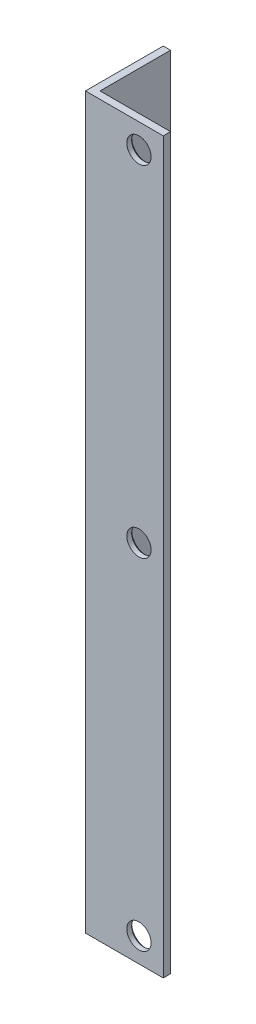
SolidWorks part; units mm, degrees
ref_plane "Спереди" through (0, 0, 0) normal (0, 0, 1) x (1, 0, 0)
ref_plane "Сверху" through (0, 0, 0) normal (0, 1, 0) x (1, 0, 0)
ref_plane "Справа" through (0, 0, 0) normal (1, 0, 0) x (0, 0, -1)
sketch "Эскиз1" plane through (0, 0, 0) normal (0, 1, 0) x (1, 0, 0)
  line L0 (0, 32) -> (0, 0)
  line L1 (0, 0) -> (32, 0)
extrude "Вытянуть-Тонкостенный1" add sketch "Эскиз1" along normal blind 300 thin thin type one direction reverse wall 3
sketch "Эскиз2" plane through (0, 0, 0) normal (0, 0, 1) x (1, 0, 0)
  circle A0 centre (22, 10) radius 5
  circle A1 centre (22, 150) radius 5
  circle A2 centre (22, 290) radius 5
extrude "Вырез-Вытянуть1" cut sketch "Эскиз2" against normal through all
chamfer "Фаска1" distance 1 angle 45 3 edges at (17, 10, -3) (17, 150, -3) (17, 290, -3)
